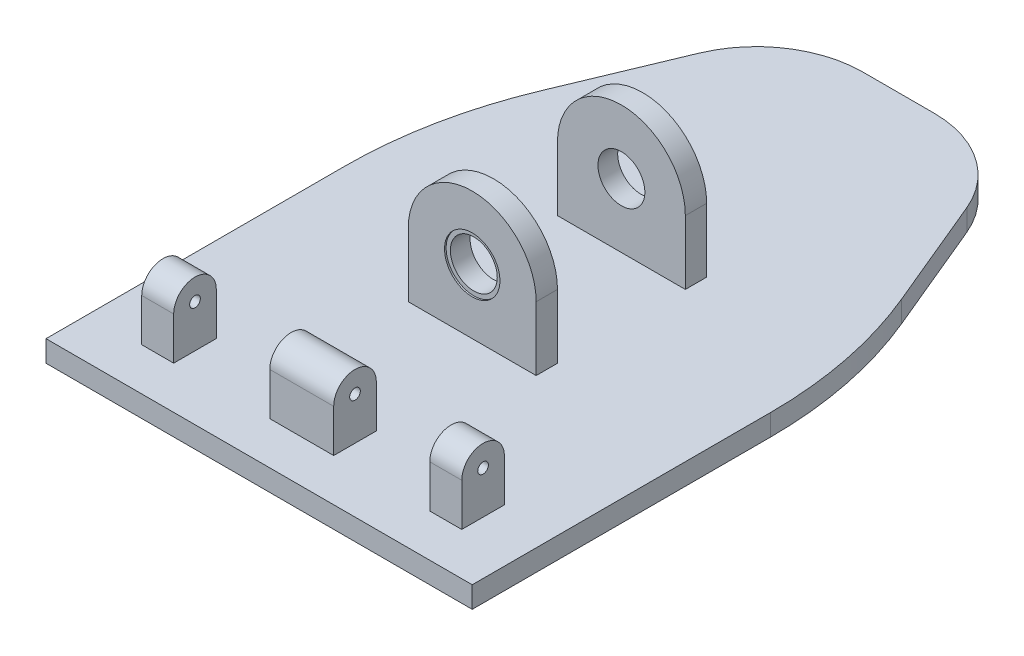
SolidWorks part; units mm, degrees
ref_plane "前视基准面" through (0, 0, 0) normal (0, 0, 1) x (1, 0, 0)
ref_plane "上视基准面" through (0, 0, 0) normal (0, 1, 0) x (1, 0, 0)
ref_plane "右视基准面" through (0, 0, 0) normal (1, 0, 0) x (0, 0, -1)
other "Configuration Table"
sketch "草图1" plane through (0, 0, 0) normal (0, 1, 0) x (1, 0, 0)
  line L0 (0, 0) -> (0, 255.8207) construction
  line L1 (-100, 0) -> (100, 0)
  line L2 (100, 0) -> (100, 180)
  line L3 (100, 180) -> (50, 300)
  line L4 (50, 300) -> (-50, 300)
  line L5 (-100, 180) -> (-50, 300)
  line L6 (-100, 0) -> (-100, 180)
  point P8 (0, 300)
  dimension "D1" = 300
  dimension "D2" = 100
  dimension "D3" = 120
  dimension "D4" = 50
extrude "凸台-拉伸1" add sketch "草图1" along normal blind 10
sketch "草图2" plane through (100, 0, 0) normal (1, 0, 0) x (0, 0, -1)
  line L0 (40, 100) -> (40, -10.3339) construction
  line L1 (0, 10) -> (0, 0) construction
  line L2 (0, 10) -> (0, 60)
  line L3 (80, 10) -> (80, 60)
  arc A0 (80, 60) -> (0, 60) centre (40, 60) ccw
  circle A1 centre (40, 60) radius 10
  line M6 (180, 10) -> (0, 10)
  dimension "D3" = 20
  dimension "D1" = 40
  dimension "D2" = 50
extrude "凸台-拉伸2" [suppressed] add sketch "草图2" against normal up to surface (200 mm away) contours A0 L0 A1 L3 M6 | L0 A0 L2 A1 M6
sketch "草图3" [suppressed] plane through (0, 10, 0) normal (0, 1, 0) x (1, 0, 0)
  line L0 (0, 0) -> (0, 135.8056) construction
  line L1 (-100, 0) -> (100, 0) construction
  line L2 (-70, 0) -> (70, 0)
  line L3 (-70, 0) -> (-70, 100)
  line L4 (-70, 100) -> (70, 100)
  line L5 (70, 0) -> (70, 100)
  line L6 (100, 0) -> (100, 80) construction
  line L7 (-100, 80) -> (-100, 0) construction
  dimension "D1" = 30
  dimension "D2" = 30
  dimension "D3" = 100
extrude "切除-拉伸1" [suppressed] cut sketch "草图3" along normal blind 171
sketch "草图4" plane through (0, 0, 0) normal (0, 0, 1) x (1, 0, 0)
  line L0 (0, 0) -> (0, 92.3322) construction
  line L1 (30, 40) -> (30, 10)
  line L2 (-30, 40) -> (-30, 10)
  line L3 (-100, 10) -> (100, 10) construction
  arc A0 (-30, 40) -> (30, 40) centre (0, 40) cw
  circle A1 centre (0, 40) radius 11
  line M10 (100, 10) -> (-100, 10)
  dimension "D2" = 30
  dimension "D3" = 22
  dimension "D1" = 30
extrude "凸台-拉伸3" add sketch "草图4" against normal blind 80 from offset 100 contours L0 L1 A0 A1 M10 | L0 A1 A0 L2 M10 region at (-15.2547, 36.8238, 0) region at (15.2547, 36.8238, 0) offset against normal yes
sketch "草图5" plane through (0, 10, 0) normal (0, 1, 0) x (1, 0, 0)
  line L0 (-47.074, 140) -> (51.1394, 140) construction
  line L1 (30, 180) -> (-30, 180) construction
  line L2 (30, 100) -> (-30, 100) construction
  line L3 (-30, 100) -> (30, 100) construction
  line L4 (-40, 170) -> (40, 170)
  line L5 (-40, 170) -> (-40, 110)
  line L6 (-40, 110) -> (40, 110)
  line L7 (40, 170) -> (40, 110)
  line L8 (30, 180) -> (30, 100) construction
  line L9 (-30, 180) -> (-30, 100) construction
  dimension "D1" = 10
  dimension "D2" = 10
  dimension "D3" = 10
  dimension "D4" = 10
extrude "切除-拉伸2" cut sketch "草图5" along normal blind 110 contours L7 L6 L5 L4
fillet "圆角1" radius 50 2 edges at (-50, 5, -300) (50, 5, -300)
fillet "圆角2" radius 200 2 edges at (-100, 5, -180) (100, 5, -180)
sketch "草图6" [suppressed] plane through (100, 0, 0) normal (1, 0, 0) x (0, 0, -1)
  line L0 (40, 60) -> (40, -52.2503) construction
  circle A0 centre (40, 60) radius 10 construction
  circle A1 centre (40, 60) radius 10 construction
  arc A2 (73.0468, 82.5368) -> (6.9532, 82.5368) centre (40, -25) ccw
  arc A3 (80, 60) -> (0, 60) centre (40, 60) ccw construction
  arc A4 (73.0468, 82.5368) -> (6.9532, 82.5368) centre (40, 60) ccw
  dimension "D2" = 225
  dimension "D1" = 25
extrude "切除-拉伸3" [suppressed] cut sketch "草图6" against normal through all both and the other way through all contours A2 A4
sketch "草图7" plane through (0, 10, 0) normal (0, 1, 0) x (1, 0, 0)
  line L0 (0, 0) -> (0, 141.3983) construction
  line L1 (-100, 0) -> (100, 0) construction
  circle A0 centre (45, 30) radius 9
  dimension "D1" = 18
  dimension "D2" = 45
  dimension "D3" = 30
extrude "切除-拉伸6" [suppressed] cut sketch "草图7" against normal offset from surface (6 mm away) 4 contours A0
sketch "草图10" [suppressed] plane through (0, 4, 0) normal (0, 1, 0) x (1, 0, 0)
  circle A0 centre (45, 30) radius 6
  dimension "D1" = 12
extrude "切除-拉伸7" [suppressed] cut sketch "草图10" against normal blind 28 contours A0
sketch "草图11" [suppressed] plane through (0, 10, 0) normal (0, 1, 0) x (1, 0, 0)
  circle A0 centre (45, 30) radius 12.5
  circle A1 centre (45, 30) radius 16.5
  dimension "D1" = 25
  dimension "D2" = 33
extrude "切除-拉伸8" [suppressed] cut sketch "草图11" against normal blind 5
sketch "草图12" [suppressed] plane through (0, 10, 0) normal (0, 1, 0) x (1, 0, 0)
  circle A0 centre (45, 30) radius 15
  dimension "D1" = 30
extrude "凸台-拉伸5" [suppressed] add sketch "草图12" along normal blind 4 contours A0
sketch "草图13" [suppressed] plane through (0, 14, 0) normal (0, 1, 0) x (1, 0, 0)
  circle A0 centre (45, 30) radius 9
  dimension "D1" = 18
extrude "切除-拉伸9" [suppressed] cut sketch "草图13" against normal blind 4
sketch "草图14" [suppressed] plane through (0, 14, 0) normal (0, 1, 0) x (1, 0, 0)
  circle A0 centre (45, 30) radius 11
  circle A1 centre (45, 30) radius 9 construction
  circle A2 centre (45, 30) radius 9 construction
  circle A3 centre (45, 30) radius 9
  dimension "D1" = 2
extrude "卡簧槽" [suppressed] cut sketch "草图14" against normal blind 1.5 from offset 2 contours A0 offset against normal yes
chamfer "倒角1" [suppressed] distance 1 angle 45
ref_plane "基准面1" through (0, 0, 0) normal (-1, 0, 0) x (0, 0, 1)
mirror "镜向1" [suppressed] about plane through (0, 0, 0) normal (-1, 0, 0)
sketch "草图16" plane through (0, 0, -100) normal (0, 0, 1) x (1, 0, 0)
  circle A0 centre (0, 40) radius 13
  dimension "D1" = 26
extrude "切除-拉伸10" cut sketch "草图16" against normal blind 0.75
sketch "草图17" plane through (0, 0, -180) normal (0, 0, -1) x (-1, 0, 0)
  circle A0 centre (0, 40) radius 13
  dimension "D1" = 26
extrude "切除-拉伸11" cut sketch "草图17" against normal blind 0.75 contours A0
sketch "草图18" plane through (-100, 0, 0) normal (-1, 0, 0) x (0, 0, 1)
  line L0 (-30, 92.2697) -> (-30, -20.0308) construction
  line L1 (-40, 10) -> (-40, 30)
  line L2 (-140, 10) -> (0, 10) construction
  line L3 (-20, 30) -> (-20, 10)
  line L4 (-40, 10) -> (-20, 10)
  arc A0 (-20, 30) -> (-40, 30) centre (-30, 30) ccw
  circle A1 centre (-30, 30) radius 2.5
  dimension "D2" = 5
  dimension "D4" = 10
  dimension "D1" = 30
  dimension "D3" = 20
extrude "凸台-拉伸6" add sketch "草图18" against normal up to surface (200 mm away) contours A1 L0 | L0 A1 | L3 L4 L1 A0 region at (-100, 30, -28.939) region at (-100, 30, -31.061) up to face at (100, 5, -70)
sketch "草图20" plane through (0, 10, 0) normal (0, 1, 0) x (1, 0, 0)
  line L0 (0, 0) -> (0, 309.5578) construction
  line L1 (-100, 0) -> (100, 0) construction
  line L2 (-60.0864, 49.2403) -> (-60.0864, 11.6041)
  line L3 (75.0864, 51.8093) -> (107.8414, 51.8093)
  line L4 (75.0864, 51.8093) -> (75.0864, 7.1083)
  line L5 (75.0864, 7.1083) -> (107.8414, 7.1083)
  line L6 (107.8414, 51.8093) -> (107.8414, 7.1083)
  line L7 (15, 49.2403) -> (60.0864, 49.2403)
  line L8 (15, 49.2403) -> (15, 11.6041)
  line L9 (15, 11.6041) -> (60.0864, 11.6041)
  line L10 (60.0864, 49.2403) -> (60.0864, 11.6041)
  line L11 (-15, 11.6041) -> (-60.0864, 11.6041)
  line L12 (-15, 49.2403) -> (-15, 11.6041)
  line L13 (-15, 49.2403) -> (-60.0864, 49.2403)
  line L14 (-107.8414, 51.8093) -> (-107.8414, 7.1083)
  line L15 (-75.0864, 7.1083) -> (-107.8414, 7.1083)
  line L16 (-75.0864, 51.8093) -> (-75.0864, 7.1083)
  line L17 (-75.0864, 51.8093) -> (-107.8414, 51.8093)
  dimension "D1" = 15
  dimension "D2" = 15
extrude "切除-拉伸12" cut sketch "草图20" along normal through all
